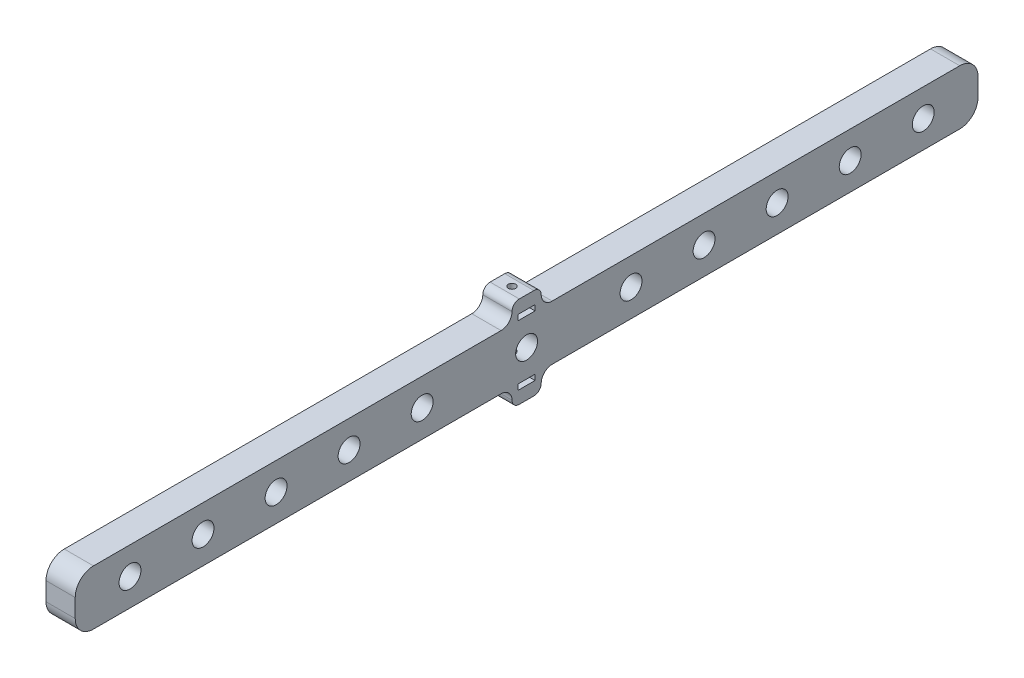
SolidWorks part; units mm, degrees
ref_plane "前视基准面" through (0, 0, 0) normal (0, 0, 1) x (1, 0, 0)
ref_plane "上视基准面" through (0, 0, 0) normal (0, 1, 0) x (1, 0, 0)
ref_plane "右视基准面" through (0, 0, 0) normal (1, 0, 0) x (0, 0, -1)
other "Configuration Table"
sketch "草图1" plane through (0, 0, 0) normal (1, 0, 0) x (0, 0, -1)
  line L1 (0, 0) -> (130, 0)
  line L2 (0, 0) -> (0, 15)
  line L3 (0, 15) -> (130, 15)
  line L4 (130, 0) -> (130, 15)
  dimension "D1" = 15
  dimension "D2" = 130
extrude "凸台-拉伸1" add sketch "草图1" along normal blind 8
sketch "草图15" plane through (0, 0, 0) normal (-1, 0, 0) x (0, 0, 1)
  line L0 (0, 15) -> (0, 0) construction
  circle A2 centre (-6.4, 7.5) radius 3
  dimension "D1" = 6
  dimension "D2" = 6.4
sketch "草图17" plane through (0, 0, 0) normal (-1, 0, 0) x (0, 0, 1)
  line L0 (-130, 7.5) -> (-31.7081, 7.5) construction
  line L1 (-130, 0) -> (-130, 15) construction
  circle A0 centre (-115, 7.5) radius 3
  circle A1 centre (-95, 7.5) radius 3
  circle A2 centre (-75, 7.5) radius 3
  circle A3 centre (-55, 7.5) radius 3
  circle A4 centre (-35, 7.5) radius 3
  dimension "D6" = 6
  dimension "D7" = 6
  dimension "D8" = 6
  dimension "D9" = 6
  dimension "D10" = 6
  dimension "D1" = 15
  dimension "D2" = 20
  dimension "D3" = 20
  dimension "D4" = 20
  dimension "D5" = 20
extrude "切除-拉伸10" cut sketch "草图17" against normal up to next
sketch "草图19" plane through (0, 0, 0) normal (0, 0, 1) x (1, 0, 0)
  line L1 (0, 15) -> (8, 15)
  line L2 (0, 15) -> (0, 0)
  line L3 (0, 0) -> (8, 0)
  line L4 (8, 15) -> (8, 0)
extrude "凸台-拉伸6" add sketch "草图19" along normal blind 117.2
ref_plane "基准面1" through (0, 0, -6.4) normal (0, 0, 1) x (1, 0, 0)
mirror "镜向1" about plane through (0, 0, -6.4) normal (0, 0, 1) of "切除-拉伸10"
fillet "圆角1" radius 5 4 edges at (4, 0, 117.2) (4, 15, 117.2) (4, 15, -130) (4, 0, -130)
extrude "切除-拉伸12" cut sketch "草图15" against normal up to next
sketch "草图22" plane through (0, 15, 0) normal (0, 1, 0) x (1, 0, 0)
  line L0 (0, 125) -> (0, -112.2) construction
  line L1 (0, 10.4) -> (8, 10.4)
  line L2 (0, 10.4) -> (0, 2.4)
  line L3 (0, 2.4) -> (8, 2.4)
  line L4 (8, 10.4) -> (8, 2.4)
  line L5 (8, 125) -> (8, -112.2) construction
  line L6 (0, 6.4) -> (8, 6.4) construction
  line L7 (0, 130) -> (8, 130) construction
  dimension "D1" = 8
  dimension "D2" = 123.6
  dimension "D3" = 4
extrude "凸台-拉伸7" add sketch "草图22" along normal blind 5
ref_plane "基准面2" through (0, 7.5, 0) normal (0, 1, 0) x (1, 0, 0)
ref_plane "基准面3" through (0, 15, 0) normal (0, 1, 0) x (1, 0, 0)
sketch "草图24" plane through (0, 15, 0) normal (0, 1, 0) x (1, 0, 0)
  line L1 (4, 4.0906) -> (6, 5.2453)
  line L2 (6, 5.2453) -> (6, 7.5547)
  line L3 (6, 7.5547) -> (4, 8.7094)
  line L4 (4, 8.7094) -> (2, 7.5547)
  line L5 (2, 7.5547) -> (2, 5.2453)
  line L6 (2, 5.2453) -> (4, 4.0906)
  circle A0 centre (4, 6.4) radius 2 construction
  dimension "D1" = 4
extrude "切除-拉伸18" cut sketch "草图24" along normal blind 1.5
sketch "草图25" plane through (8, 0, 0) normal (1, 0, 0) x (0, 0, -1)
  line L0 (6.4, 20) -> (6.4, 15) construction
  line L1 (2.4, 20) -> (10.4, 20) construction
  line L2 (4.4, 15) -> (-4.4, 15) construction
  line L4 (4.09, 15) -> (8.71, 15)
  line L5 (4.09, 15) -> (4.09, 16.5)
  line L6 (4.09, 16.5) -> (8.71, 16.5)
  line L7 (8.71, 15) -> (8.71, 16.5)
  dimension "D1" = 1.5
  dimension "D2" = 4.62
  dimension "D3" = 2.31
extrude "切除-拉伸19" cut sketch "草图25" against normal blind 4 contours L5 L6 L7 L4
fillet "圆角8" radius 3 2 edges at (4, 15, -10.4) (4, 15, -2.4)
fillet "圆角9" radius 2 2 edges at (4, 20, -2.4) (4, 20, -10.4)
mirror "镜向6" about plane through (0, 7.5, 0) normal (0, 1, 0) of "切除-拉伸19", "切除-拉伸18", "凸台-拉伸7"
fillet "圆角10" radius 2 2 edges at (4, -5, -2.4) (4, -5, -10.4)
fillet "圆角11" radius 3 2 edges at (4, 0, -2.4) (4, 0, -10.4)
sketch "草图21" plane through (0, 15, 0) normal (0, 1, 0) x (1, 0, 0)
  line L0 (0, 6.4) -> (8, 6.4) construction
  line L4 (0, 125) -> (0, 13.4) construction
  line L5 (8, 125) -> (8, 13.4) construction
  line L6 (0, 130) -> (8, 130) construction
  circle A0 centre (4, 6.4) radius 1
  dimension "D2" = 2
  dimension "D1" = 123.6
extrude "切除-拉伸20" cut sketch "草图21" against normal blind 28.5 and the other way blind 15.5
